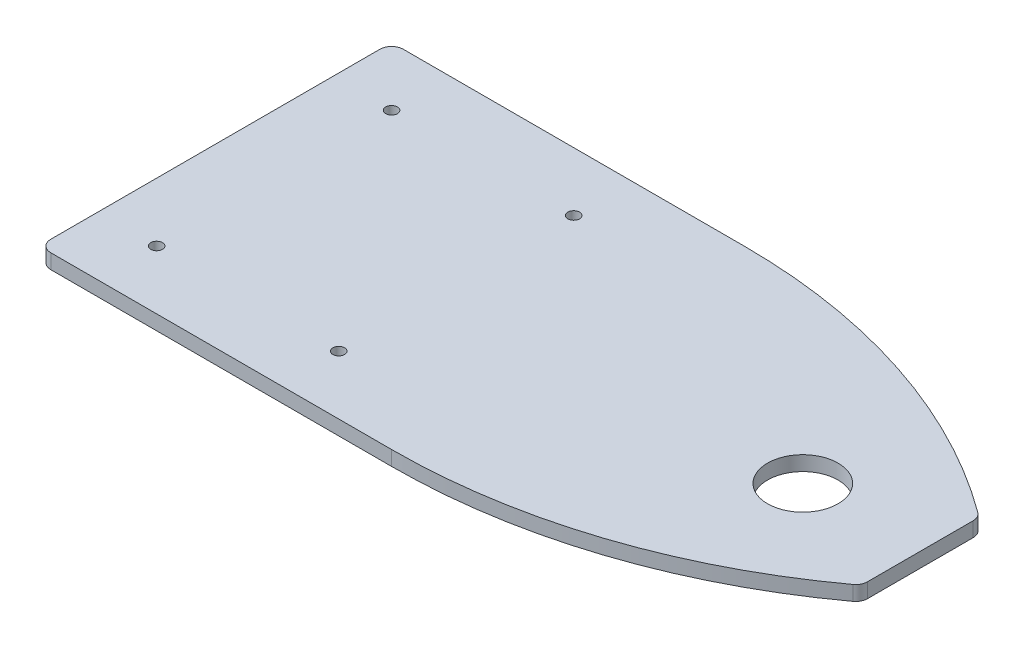
SolidWorks part; units mm, degrees
material "PLA"
ref_plane "Front" through (0, 0, 0) normal (0, 0, 1) x (1, 0, 0)
ref_plane "Top" through (0, 0, 0) normal (0, 1, 0) x (1, 0, 0)
ref_plane "Right" through (0, 0, 0) normal (1, 0, 0) x (0, 0, -1)
sketch "Sketch1" plane through (0, 0, 0) normal (0, 1, 0) x (1, 0, 0)
  line L1 (76.2, -38.1) -> (-76.2, -38.1)
  line L2 (76.2, -38.1) -> (76.2, 38.1)
  line L3 (76.2, 38.1) -> (-76.2, 38.1)
  line L4 (-76.2, -38.1) -> (-76.2, 38.1)
  line L5 (76.2, -38.1) -> (-76.2, 38.1) construction
  line L6 (76.2, 38.1) -> (-76.2, -38.1) construction
  point P0 (0, 0)
  dimension "D1" = 76.2
  dimension "D2" = 152.4
extrude "Boss-Extrude1" add sketch "Sketch1" along normal blind 3.175
sketch "Sketch4" plane through (0, 3.175, 0) normal (0, 1, 0) x (1, 0, 0)
  line L0 (0, 38.1) -> (76.2, 38.1)
  line L1 (76.2, 38.1) -> (-76.2, 38.1) construction
  line L2 (76.2, 38.1) -> (76.2, 12.7)
  line L3 (76.2, -38.1) -> (76.2, 38.1) construction
  line L4 (76.2, -38.1) -> (76.2, -12.7)
  line L5 (76.2, -38.1) -> (0, -38.1)
  line L6 (-76.2, -38.1) -> (76.2, -38.1) construction
  arc A0 (0, -38.1) -> (76.2, -12.7) centre (0, 88.9) ccw
  arc A1 (0, 38.1) -> (76.2, 12.7) centre (0, -88.9) cw
  dimension "D3" = 127
  dimension "D4" = 127
  dimension "D1" = 25.4
  dimension "D2" = 25.4
extrude "Cut-Extrude1" cut sketch "Sketch4" against normal blind 3.175
fillet "Fillet2" radius 2.54 2 edges at (76.2, 1.5875, 12.7) (76.2, 1.5875, -12.7)
fillet "Fillet3" radius 2.54 2 edges at (-76.2, 1.5875, 38.1) (-76.2, 1.5875, -38.1)
sketch "Sketch5" plane through (0, 3.175, 0) normal (0, 1, 0) x (1, 0, 0)
  line L0 (-55, 0) -> (55, 0) construction
  line L1 (76.2, -11.422) -> (76.2, 11.422) construction
  circle A0 centre (50.8, 0) radius 7.62
  dimension "D1" = 15.24
  dimension "D2" = 25.4
extrude "Cut-Extrude2" cut sketch "Sketch5" against normal blind 3.175
sketch "Sketch6" plane through (0, 3.175, 0) normal (0, 1, 0) x (1, 0, 0)
  line L0 (0, 38.1) -> (-73.66, 38.1) construction
  line L1 (-73.66, -38.1) -> (0, -38.1) construction
  line L2 (-76.2, 35.56) -> (-76.2, -35.56) construction
  circle A0 centre (-63.5, 25.4) radius 1.27
  circle A1 centre (-63.5, -25.4) radius 1.27
  circle A2 centre (-24.13, 25.4) radius 1.27
  circle A3 centre (-24.13, -25.4) radius 1.27
  dimension "D1" = 2.54
  dimension "D2" = 2.54
  dimension "D4" = 12.7
  dimension "D7" = 2.54
  dimension "D8" = 2.54
  dimension "D3" = 12.7
  dimension "D5" = 12.7
  dimension "D6" = 12.7
  dimension "D9" = 39.37
  dimension "D10" = 39.37
extrude "Cut-Extrude3" cut sketch "Sketch6" against normal blind 3.175
